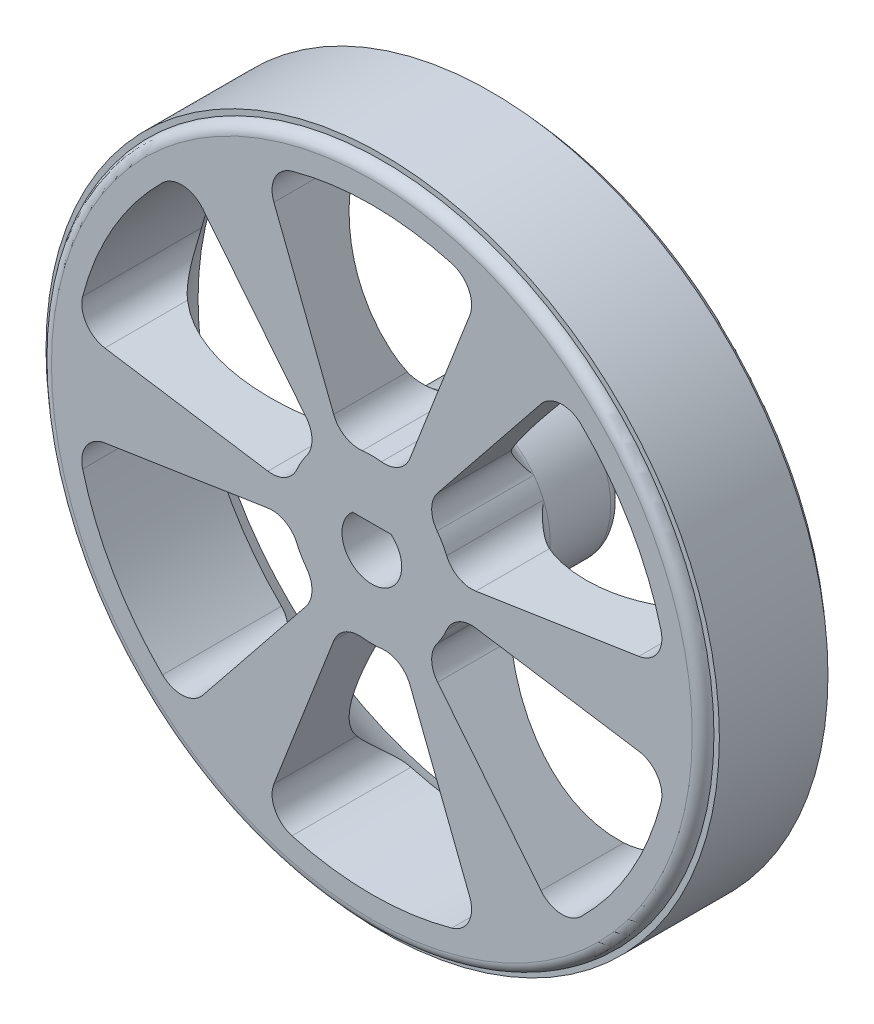
SolidWorks part; units mm, degrees
ref_plane "Plan de face" through (0, 0, 0) normal (0, 0, 1) x (1, 0, 0)
ref_plane "Plan de dessus" through (0, 0, 0) normal (0, 1, 0) x (1, 0, 0)
ref_plane "Plan de droite" through (0, 0, 0) normal (1, 0, 0) x (0, 0, -1)
sketch "Esquisse2" plane through (0, 0, 0) normal (1, 0, 0) x (0, 0, -1)
  line L0 (-81.0256, 0) -> (80.5128, 0) construction
  line L1 (0, 0) -> (0, 30.5)
  line L2 (0, 30.5) -> (1, 30.5)
  line L3 (1, 30.5) -> (1, 30)
  line L4 (1, 30) -> (11, 30)
  line L5 (11, 30) -> (11, 30.5)
  line L6 (11, 30.5) -> (12, 30.5)
  line L7 (12, 30.5) -> (12, 28)
  line L8 (0, 0) -> (15.5, 0)
  line L9 (8.918, 7.5) -> (15.5, 7.5)
  line L10 (15.5, 7.5) -> (15.5, 0)
  line L11 (15.5, 0) -> (0, 0)
  line L12 (5, 15.2695) -> (5, -4.7992) construction
  spline S0 degree 3 poles (12, 28) (0.2522, 23.011) (6.2493, 7.4817) (8.918, 7.5) knots 0 0 0 0 1 1 1 1
  dimension "D1" = 30.5
  dimension "D2" = 0.5
  dimension "D3" = 1
  dimension "D4" = 10
  dimension "D5" = 7.5
  dimension "D6" = 5
  dimension "D7" = 2.5
  dimension "D8" = 15.5
revolve "Révolution1" add sketch "Esquisse2" angle 360 about L11 region at (0, 13.1189, -5.4967)
sketch "Esquisse3" plane through (0, 0, 0) normal (0, 0, 1) x (1, 0, 0)
  line L0 (0, 35.1948) -> (0, -41.5842) construction
  line L1 (-46.9619, 0) -> (52.0734, 0) construction
  line L2 (0, 0) -> (-20.3739, 52.3915) construction
  line L3 (0, 0) -> (20.3739, 52.3915) construction
  line L4 (-9.0155, 23.1834) -> (-3.5093, 9.0241)
  line L5 (3.5093, 9.0241) -> (9.0155, 23.1834)
  line L6 (9.5698, 1.4729) -> (24.5852, 3.784)
  line L7 (15.5696, 19.3994) -> (6.0605, 7.5512)
  line L8 (6.0605, -7.5512) -> (15.5696, -19.3994)
  line L9 (24.5852, -3.784) -> (9.5698, -1.4729)
  line L10 (-3.5093, -9.0241) -> (-9.0155, -23.1834)
  line L11 (9.0155, -23.1834) -> (3.5093, -9.0241)
  line L12 (-9.5698, -1.4729) -> (-24.5852, -3.784)
  line L13 (-15.5696, -19.3994) -> (-6.0605, -7.5512)
  line L14 (-6.0605, 7.5512) -> (-15.5696, 19.3994)
  line L15 (-24.5852, 3.784) -> (-9.5698, 1.4729)
  arc A0 (-7.3541, 26.4984) -> (7.3541, 26.4984) centre (0, 0) cw
  circle A1 centre (0, 0) radius 30.5
  circle A2 centre (0, 0) radius 30.5
  arc A3 (-0.8845, 7.4477) -> (0.8845, 7.4477) centre (0, 0) cw
  arc A4 (-0.8845, 7.4477) -> (-3.5093, 9.0241) centre (-1.1793, 9.9302) cw
  arc A5 (0.8845, 7.4477) -> (3.5093, 9.0241) centre (1.1793, 9.9302) ccw
  arc A6 (7.3541, 26.4984) -> (9.0155, 23.1834) centre (6.6855, 24.0895) cw
  arc A7 (-7.3541, 26.4984) -> (-9.0155, 23.1834) centre (-6.6855, 24.0895) ccw
  arc A8 (26.6254, 6.8804) -> (24.5852, 3.784) centre (24.2049, 6.2549) cw
  arc A9 (6.8921, 2.9579) -> (9.5698, 1.4729) centre (9.1895, 3.9438) ccw
  arc A10 (19.2713, 19.618) -> (26.6254, 6.8804) centre (0, 0) cw
  arc A11 (19.2713, 19.618) -> (15.5696, 19.3994) centre (17.5194, 17.8346) ccw
  arc A12 (6.0076, 4.4898) -> (6.0605, 7.5512) centre (8.0102, 5.9864) cw
  arc A13 (6.0076, 4.4898) -> (6.8921, 2.9579) centre (0, 0) cw
  arc A14 (19.2713, -19.618) -> (15.5696, -19.3994) centre (17.5194, -17.8346) cw
  arc A15 (6.0076, -4.4898) -> (6.0605, -7.5512) centre (8.0102, -5.9864) ccw
  arc A16 (26.6254, -6.8804) -> (19.2713, -19.618) centre (0, 0) cw
  arc A17 (26.6254, -6.8804) -> (24.5852, -3.784) centre (24.2049, -6.2549) ccw
  arc A18 (6.8921, -2.9579) -> (9.5698, -1.4729) centre (9.1895, -3.9438) cw
  arc A19 (6.8921, -2.9579) -> (6.0076, -4.4898) centre (0, 0) cw
  arc A20 (-7.3541, -26.4984) -> (-9.0155, -23.1834) centre (-6.6855, -24.0895) cw
  arc A21 (-0.8845, -7.4477) -> (-3.5093, -9.0241) centre (-1.1793, -9.9302) ccw
  arc A22 (7.3541, -26.4984) -> (-7.3541, -26.4984) centre (0, 0) cw
  arc A23 (7.3541, -26.4984) -> (9.0155, -23.1834) centre (6.6855, -24.0895) ccw
  arc A24 (0.8845, -7.4477) -> (3.5093, -9.0241) centre (1.1793, -9.9302) cw
  arc A25 (0.8845, -7.4477) -> (-0.8845, -7.4477) centre (0, 0) cw
  arc A26 (-26.6254, -6.8804) -> (-24.5852, -3.784) centre (-24.2049, -6.2549) cw
  arc A27 (-6.8921, -2.9579) -> (-9.5698, -1.4729) centre (-9.1895, -3.9438) ccw
  arc A28 (-19.2713, -19.618) -> (-26.6254, -6.8804) centre (0, 0) cw
  arc A29 (-19.2713, -19.618) -> (-15.5696, -19.3994) centre (-17.5194, -17.8346) ccw
  arc A30 (-6.0076, -4.4898) -> (-6.0605, -7.5512) centre (-8.0102, -5.9864) cw
  arc A31 (-6.0076, -4.4898) -> (-6.8921, -2.9579) centre (0, 0) cw
  arc A32 (-19.2713, 19.618) -> (-15.5696, 19.3994) centre (-17.5194, 17.8346) cw
  arc A33 (-6.0076, 4.4898) -> (-6.0605, 7.5512) centre (-8.0102, 5.9864) ccw
  arc A34 (-26.6254, 6.8804) -> (-19.2713, 19.618) centre (0, 0) cw
  arc A35 (-26.6254, 6.8804) -> (-24.5852, 3.784) centre (-24.2049, 6.2549) ccw
  arc A36 (-6.8921, 2.9579) -> (-9.5698, 1.4729) centre (-9.1895, 3.9438) cw
  arc A37 (-6.8921, 2.9579) -> (-6.0076, 4.4898) centre (0, 0) cw
  point P18 (-2.7183, 6.9901)
  point P21 (2.7183, 6.9901)
  point P24 (9.967, 25.6302)
  point P27 (-9.967, 25.6302)
  point P91 (0, 0)
  dimension "D3" = 20
  dimension "D5" = 2.5
  dimension "D2" = 42.5
  dimension "D4" = 27.5
  dimension "D1" = 0
  dimension "D6" = 6
extrude "Enlèv. mat.-Extru.1" cut sketch "Esquisse3" against normal through all both and the other way through all flip side to cut
sketch "Esquisse4" plane through (0, 0, -15.5) normal (0, 0, -1) x (-1, 0, 0)
  line L0 (-36.119, 0) -> (40.115, 0) construction
  line L1 (-1.7702, 2.1045) -> (1.7702, 2.1045)
  circle A0 centre (0, 0) radius 2.75 construction
  circle A1 centre (0, 0) radius 7.5
  circle A2 centre (0, 0) radius 7.5
  arc A3 (-1.7702, 2.1045) -> (1.7702, 2.1045) centre (0, 0) ccw
  dimension "D2" = 2.1045
  dimension "D3" = 5.5
  dimension "D1" = 0
extrude "Enlèv. mat.-Extru.2" cut sketch "Esquisse4" against normal through all contours L1 A3 region at (0, -0.1666, -15.5)
fillet "Congé1" radius 1 1 edges at (-7.5, 0, -15.5)
fillet "Congé2" radius 1 2 edges at (-30.5, 0, -12) (-30.5, 0, 0)
sketch "Esquisse5" plane through (0, 0, 0) normal (1, 0, 0) x (0, 0, -1)
  line L0 (11, 30) -> (11, 31)
  line L1 (11, 31) -> (1, 31)
  line L2 (1, 31) -> (1, 30)
  line L3 (1, 30) -> (11, 30)
  line L4 (-10.7888, 0) -> (37.3247, 0) construction
  dimension "D1" = 1
revolve "pneue" add sketch "Esquisse5" angle 360 about L4
sketch "Esquisse6" plane through (0, 0, 0) normal (0, 1, 0) x (1, 0, 0)
  line L0 (0, 24.3861) -> (0, -19.9274) construction
  line L1 (1.7702, 15.5) -> (-1.7702, 15.5) construction
  line L2 (1.7702, 15.5) -> (-1.7702, 15.5)
  circle A0 centre (0, 13) radius 1.55
  dimension "D1" = 2.5
  dimension "D2" = 3.1
extrude "Enlèv. mat.-Extru.3" cut sketch "Esquisse6" along normal blind 10 contours A0
sketch "Esquisse7" plane through (0, 0, 0) normal (0, 1, 0) x (1, 0, 0)
  line L0 (1.7702, 15.5) -> (-1.7702, 15.5) construction
  line L1 (1.7702, 15.5) -> (-1.7702, 15.5) construction
  line L6 (-3.5, 15.5) -> (-3.5, 13)
  line L7 (6.5, 15.5) -> (-6.5, 15.5) construction
  line L8 (-3.5, 13) -> (3.5, 13) construction
  line L9 (3.5, 13) -> (3.5, 15.5)
  line L10 (2.75, 15.5) -> (-2.75, 15.5) construction
  line L11 (-3.5, 15.5) -> (3.5, 15.5)
  circle A0 centre (0, 13) radius 1.55 construction
  circle A1 centre (0, 13) radius 1.55 construction
  circle A2 centre (0, 13) radius 3.5 construction
  arc A3 (-3.5, 13) -> (3.5, 13) centre (0, 13) ccw
  dimension "D1" = 7
extrude "Enlèv. mat.-Extru.4" cut sketch "Esquisse7" along normal blind 10 from offset 4.6 contours L6 A3 L9 L11 region at (0, 0, -12.8174)
